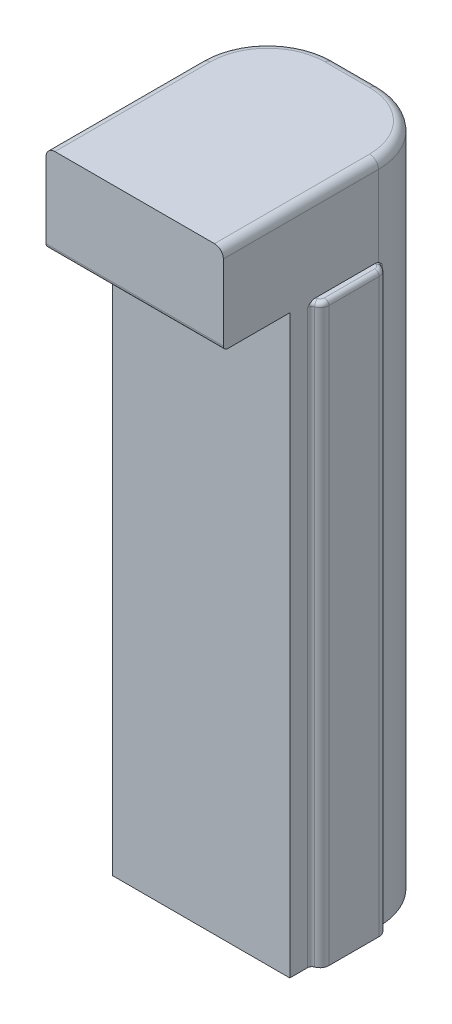
SolidWorks part; units mm, degrees
ref_plane "前视基准面" through (0, 0, 0) normal (0, 0, 1) x (1, 0, 0)
ref_plane "上视基准面" through (0, 0, 0) normal (0, 1, 0) x (1, 0, 0)
ref_plane "右视基准面" through (0, 0, 0) normal (1, 0, 0) x (0, 0, -1)
other "Configuration Table"
sketch "草图1" plane through (0, 0, 0) normal (0, 1, 0) x (1, 0, 0)
  line L1 (20, 37.0054) -> (-20, 37.0054)
  line L2 (20, 37.0054) -> (20, -12.9946)
  line L3 (20, -12.9946) -> (-20, -12.9946)
  line L4 (-20, 37.0054) -> (-20, -12.9946)
  dimension "D2" = 40
  dimension "D3" = 50
extrude "凸台-拉伸1" add sketch "草图1" along normal blind 20
sketch "草图2" plane through (0, 0, 0) normal (0, -1, 0) x (1, 0, 0)
  line L0 (20, 12.9946) -> (20, -37.0054) construction
  line L1 (-20, -37.0054) -> (20, -37.0054)
  line L2 (-20, -37.0054) -> (-20, -2.0054)
  line L3 (-20, -2.0054) -> (20, -2.0054)
  line L4 (20, -37.0054) -> (20, -2.0054)
  dimension "D1" = 35
extrude "凸台-拉伸2" add sketch "草图2" along normal blind 150
fillet "圆角1" radius 15 2 edges at (20, -65, -37.0054) (-20, -65, -37.0054)
sketch "草图3" plane through (0, -150, 0) normal (0, -1, 0) x (1, 0, 0)
  line L1 (-20, -2.0054) -> (20, -2.0054)
  line L2 (-20, -2.0054) -> (-20, -62.0054)
  line L3 (-20, -62.0054) -> (20, -62.0054)
  line L4 (20, -2.0054) -> (20, -62.0054)
  dimension "D1" = 60
extrude "凸台-拉伸3" add sketch "草图3" along normal blind 10
sketch "草图5" plane through (-20, 0, 0) normal (-1, 0, 0) x (0, 0, 1)
  line L1 (-12.0054, 0) -> (-7.0054, 0)
  line L2 (-12.0054, 0) -> (-12.0054, -160)
  line L3 (-12.0054, -160) -> (-7.0054, -160)
  line L4 (-7.0054, 0) -> (-7.0054, -160)
  dimension "D1" = 5
extrude "凸台-拉伸4" add sketch "草图5" along normal blind 2
mirror "镜向1" about plane through (0, 0, 0) normal (1, 0, 0) of "凸台-拉伸4"
shell "抽壳1" thickness 3 removed face at (0, -160, -17.0054)
fillet "圆角5" radius 2 5 edges at (20, 20, -4.5054) (0, 20, -37.0054) (15.6066, 20, -32.612) (-15.6066, 20, -32.612) (-20, 20, -4.5054)
fillet "圆角7" radius 1 1 edges at (0, 0, 12.9946)
sketch "草图6" plane through (-20, 0, 0) normal (-1, 0, 0) x (0, 0, 1)
  line L1 (-62.0054, -150) -> (-2.0054, -150)
  line L2 (-62.0054, -150) -> (-62.0054, -160)
  line L3 (-62.0054, -160) -> (-2.0054, -160)
  line L4 (-2.0054, -150) -> (-2.0054, -160)
extrude "切除-拉伸2" cut sketch "草图6" against normal mid plane 135
sketch "草图9" plane through (-20, 0, 0) normal (-1, 0, 0) x (0, 0, 1)
  line L0 (12.9946, 20) -> (12.9946, -130)
  line L2 (12.9946, -130) -> (-52.5042, -130)
  line L3 (12.9946, -130) -> (12.9946, -152.8679)
  line L4 (12.9946, -152.8679) -> (-52.5042, -152.8679)
  line L5 (-52.5042, -130) -> (-52.5042, -152.8679)
  line M2 (-22.0054, 18) -> (-22.0054, -150)
  line M3 (-22.0054, -150) -> (-12.0054, -150)
  line M4 (-12.0054, -150) -> (-12.0054, 0)
  line M8 (-7.0054, 0) -> (-7.0054, -150)
  line M9 (-7.0054, -150) -> (-2.0054, -150)
  line M10 (-2.0054, -150) -> (-2.0054, 0)
  dimension "D1" = 150
extrude "切除-拉伸3" cut sketch "草图9" against normal mid plane 135 contours L2 L5 L4 L3 M10 M9 M8 M4 M3 M2 | L2 M4 M2 M3 | L2 M10 M8 M9 region at (-20, -141.4339, 12.3008) region at (-20, -140, -4.5054) region at (-20, -140, -17.0054)
sketch "草图10" plane through (0, 0, 0) normal (0, -1, 0) x (1, 0, 0)
  circle A0 centre (0, 4.9946) radius 2.25
  dimension "D1" = 4.5
extrude "切除-拉伸4" cut sketch "草图10" against normal blind 10
sketch "草图11" plane through (-22, 0, 0) normal (-1, 0, 0) x (0, 0, 1)
  line L1 (-12.0054, 0) -> (-22.0054, 0)
  line L2 (-12.0054, 0) -> (-12.0054, -130)
  line L3 (-12.0054, -130) -> (-22.0054, -130)
  line L4 (-22.0054, 0) -> (-22.0054, -130)
extrude "凸台-拉伸5" add sketch "草图11" against normal blind 4
mirror "镜向2" about plane through (0, 0, 0) normal (1, 0, 0) of "凸台-拉伸5"
fillet "圆角11" radius 1 1 edges at (-20, -65, -7.0054)
fillet "圆角12" radius 1 1 edges at (-22, -65, -7.0054)
fillet "圆角13" radius 1 1 edges at (-20, -65, -22.0054)
fillet "圆角14" radius 2 1 edges at (-22, -65, -22.0054)
fillet "圆角15" radius 1 5 edges at (-20.174, 0, -22.3985) (-20.2929, 0, -6.7126) (-21.7071, 0, -7.2983) (-22, 0, -14.0858) (-21.6266, 0, -21.3299)
fillet "圆角16" radius 1 1 edges at (20, -65, -7.0054)
fillet "圆角17" radius 2 1 edges at (22, -65, -7.0054)
fillet "圆角18" radius 1 1 edges at (20, -65, -22.0054)
fillet "圆角19" radius 2 1 edges at (22, -65, -22.0054)
fillet "圆角20" radius 1 5 edges at (20.1835, 0, -6.5828) (20.174, 0, -22.3985) (21.633, 0, -7.6792) (22, 0, -14.5) (21.6266, 0, -21.3299)
sketch "草图12" plane through (0, -130, 0) normal (0, -1, 0) x (1, 0, 0)
  line L6 (22, -20.1662) -> (22, -8.8339)
  line L7 (20, -6.0054) -> (20, -2.0054)
  line L8 (20, -2.0054) -> (-20, -2.0054)
  line L9 (-20, -2.0054) -> (-20, -6.0054)
  line L10 (-22, -8.0054) -> (-22, -20.1662)
  line L11 (-5, -37.0054) -> (5, -37.0054)
  line L12 (22, -20.1662) -> (22, -8.8339)
  line L13 (20, -6.0054) -> (20, -2.0054)
  line L14 (20, -2.0054) -> (-20, -2.0054)
  line L15 (-20, -2.0054) -> (-20, -6.0054)
  line L16 (-22, -8.0054) -> (-22, -20.1662)
  line L17 (-5, -37.0054) -> (5, -37.0054)
  arc A10 (20.6458, -22.059) -> (19.9707, -22.9429) centre (20.9687, -23.0054) ccw
  arc A11 (20.6458, -22.059) -> (22, -20.1662) centre (20, -20.1662) ccw
  arc A12 (22, -8.8339) -> (20.6667, -6.9483) centre (20, -8.8339) ccw
  arc A13 (20, -6.0054) -> (20.6667, -6.9483) centre (21, -6.0054) ccw
  arc A14 (-21, -7.0054) -> (-20, -6.0054) centre (-21, -6.0054) ccw
  arc A15 (-21, -7.0054) -> (-22, -8.0054) centre (-21, -8.0054) ccw
  arc A16 (-22, -20.1662) -> (-20.6458, -22.059) centre (-20, -20.1662) ccw
  arc A17 (-19.9707, -22.9429) -> (-20.6458, -22.059) centre (-20.9687, -23.0054) ccw
  arc A18 (-19.9707, -22.9429) -> (-5, -37.0054) centre (-5, -22.0054) ccw
  arc A19 (5, -37.0054) -> (19.9707, -22.9429) centre (5, -22.0054) ccw
  arc A20 (20.6458, -22.059) -> (19.9707, -22.9429) centre (20.9687, -23.0054) ccw
  arc A21 (20.6458, -22.059) -> (22, -20.1662) centre (20, -20.1662) ccw
  arc A22 (22, -8.8339) -> (20.6667, -6.9483) centre (20, -8.8339) ccw
  arc A23 (20, -6.0054) -> (20.6667, -6.9483) centre (21, -6.0054) ccw
  arc A24 (-21, -7.0054) -> (-20, -6.0054) centre (-21, -6.0054) ccw
  arc A25 (-21, -7.0054) -> (-22, -8.0054) centre (-21, -8.0054) ccw
  arc A26 (-22, -20.1662) -> (-20.6458, -22.059) centre (-20, -20.1662) ccw
  arc A27 (-19.9707, -22.9429) -> (-20.6458, -22.059) centre (-20.9687, -23.0054) ccw
  arc A28 (-19.9707, -22.9429) -> (-5, -37.0054) centre (-5, -22.0054) ccw
  arc A29 (5, -37.0054) -> (19.9707, -22.9429) centre (5, -22.0054) ccw
  dimension "D1" = 0
extrude "凸台-拉伸6" add sketch "草图12" against normal blind 3
